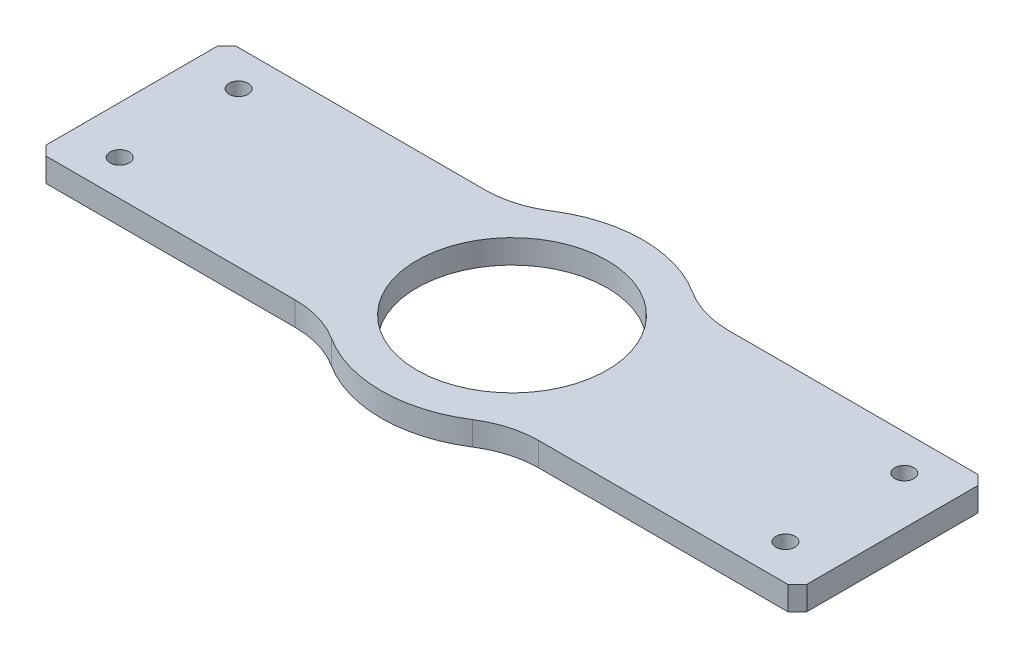
SolidWorks part; units mm, degrees
material "6061-T6 (SS)"
ref_plane "Front" through (0, 0, 0) normal (0, 0, 1) x (1, 0, 0)
ref_plane "Top" through (0, 0, 0) normal (0, 1, 0) x (1, 0, 0)
ref_plane "Right" through (0, 0, 0) normal (1, 0, 0) x (0, 0, -1)
sketch "Sketch1" plane through (0, 0, 0) normal (0, 1, 0) x (1, 0, 0)
  line L0 (203.2, 0) -> (203.2, 19.05) construction
  line L1 (0, 0) -> (69.0659, 0)
  line L2 (0, 0) -> (0, 50.8)
  line L3 (0, 50.8) -> (69.0659, 50.8)
  line L4 (203.2, 0) -> (203.2, 50.8)
  line L5 (0, 50.8) -> (203.2, 0) construction
  line L6 (134.1341, 50.8) -> (203.2, 50.8)
  line L7 (134.1341, 0) -> (203.2, 0)
  arc A0 (82.7645, -4.0105) -> (120.4355, -4.0105) centre (101.6, 25.4) ccw
  arc A1 (120.4355, 54.8105) -> (82.7645, 54.8105) centre (101.6, 25.4) ccw
  arc A2 (69.0659, 0) -> (82.7645, -4.0105) centre (69.0659, -25.4) cw
  arc A3 (134.1341, 0) -> (120.4355, -4.0105) centre (134.1341, -25.4) ccw
  arc A4 (134.1341, 50.8) -> (120.4355, 54.8105) centre (134.1341, 76.2) cw
  arc A5 (69.0659, 50.8) -> (82.7645, 54.8105) centre (69.0659, 76.2) ccw
  point P18 (125.5707, 50.8)
  dimension "D2" = 69.85
  dimension "D3" = 25.4
  dimension "D1" = 50.8
extrude "Boss-Extrude1" add sketch "Sketch1" along normal blind 6.35
sketch "Sketch4" plane through (0, 6.35, 0) normal (0, 1, 0) x (1, 0, 0)
  line L0 (0, 0) -> (12.7, 9.525) construction
  line L1 (0, 0) -> (69.0659, 0) construction
  line L6 (12.7, 9.525) -> (12.7, 41.275) construction
  line L7 (12.7, 41.275) -> (25.4, 50.8) construction
  line L8 (69.0659, 50.8) -> (0, 50.8) construction
  line L9 (101.6, 0) -> (101.6, 25.4) construction
  arc A0 (82.7645, -4.0105) -> (120.4355, -4.0105) centre (101.6, 25.4) ccw construction
  point P0 (12.7, 41.275)
  point P4 (12.7, 9.525)
  point P34 (190.5, 9.525)
  point P36 (190.5, 41.275)
  dimension "D1" = 31.75
  dimension "D2" = 25.4
hole_wizard "#10 Clearance Hole1" positions "Sketch4" profile "Sketch3" hole size "#10" standard "ANSI Inch" end condition up to next
sketch "Sketch3" plane through (12.7, 6.35, -41.275) normal (1, 0, 0) x (0, 0, 1)
  line L0 (0, 0) -> (0, 6.35)
  line L1 (0, 6.35) -> (2.5527, 6.35)
  line L2 (2.5527, 6.35) -> (2.5527, 0)
  line L5 (2.5527, 0) -> (0, 0)
  line L11 (0, -6.35) -> (0, 107.95) construction
  dimension "Thru Hole Dia." = 5.1054
  dimension "Thru Hole Depth" = 6.35
sketch "Sketch5" plane through (0, 6.35, 0) normal (0, 1, 0) x (1, 0, 0)
  circle A0 centre (101.6, 25.4) radius 25.4
  arc A1 (120.4355, 54.8105) -> (82.7645, 54.8105) centre (101.6, 25.4) ccw construction
  dimension "D1" = 50.8
extrude "Cut-Extrude1" cut sketch "Sketch5" against normal through all
chamfer "Chamfer1" distance 2.54 angle 45 4 edges at (0, 3.175, -50.8) (203.2, 3.175, -50.8) (203.2, 3.175, 0) (0, 3.175, 0)
